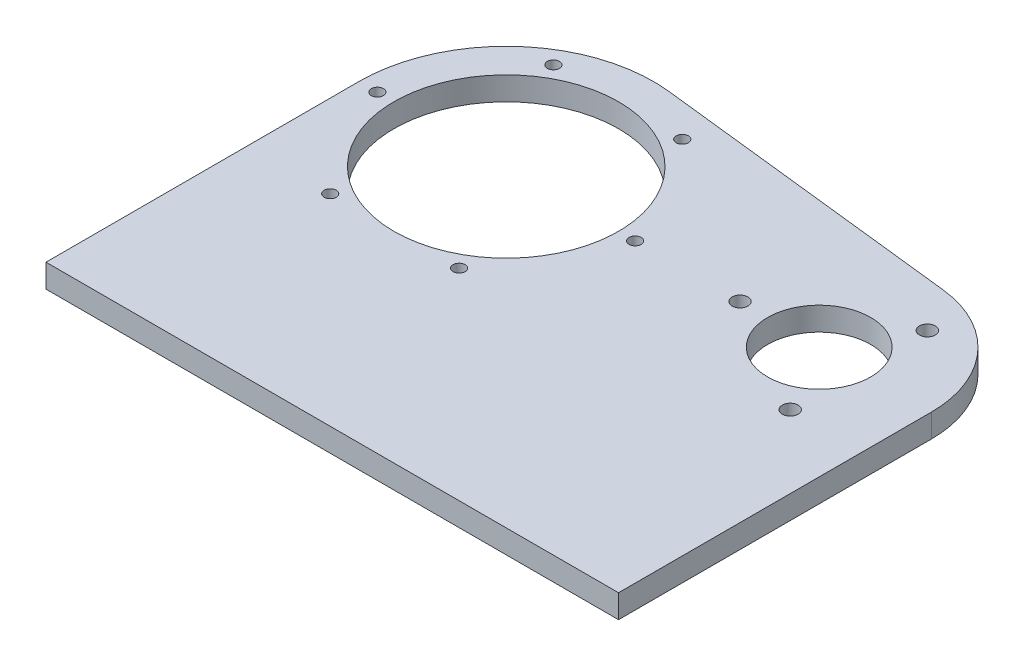
SolidWorks part; units mm, degrees
material "6061 Alloy"
ref_plane "Front Plane" through (0, 0, 0) normal (0, 0, 1) x (1, 0, 0)
ref_plane "Top Plane" through (0, 0, 0) normal (0, 1, 0) x (1, 0, 0)
ref_plane "Right Plane" through (0, 0, 0) normal (1, 0, 0) x (0, 0, -1)
sketch "Sketch1" plane through (0, 0, 0) normal (0, 1, 0) x (1, 0, 0)
  line L0 (4.4706, 39.7494) -> (88.4088, 30.3089)
  line L1 (-40, 40) -> (115.5, 40)
  line L2 (-40, 40) -> (-40, -85)
  line L3 (-40, -85) -> (115.5, -85)
  line L4 (115.5, 40) -> (115.5, -85)
  line L5 (-40, 40) -> (115.5, -85) construction
  line L6 (-40, -85) -> (115.5, 40) construction
  circle A0 centre (0, 0) radius 40
  circle A1 centre (0, 0) radius 30.5
  circle A2 centre (85, 0) radius 14
  circle A3 centre (85, 0) radius 30.5
  point P4 (37.75, -22.5)
  dimension "D3" = 80
  dimension "D4" = 61
  dimension "D5" = 61
  dimension "D6" = 28
  dimension "D1" = 85
  dimension "D7" = 85
extrude "Boss-Extrude1" add sketch "Sketch1" along normal mid plane 6.35 contours L4 A3 L1 A0 L2 L3 | A0 A1 | A3 A2 region at (41.2029, 0, 46.4583) region at (28.9795, 0, -25.9029) region at (107.0969, 0, -19.751)
hole_wizard "M4x0.7 Tapped Hole1" positions "Sketch4" profile "Sketch5" tap size "M4x0.7" standard "ANSI Metric" end condition up to next
sketch "Sketch4" plane through (0, 3.175, 0) normal (0, 1, 0) x (1, 0, 0)
  line L0 (0, 0) -> (35, 0)
  line L1 (0, 0) -> (17.5, -30.3109)
  line L2 (0, 0) -> (-17.5, -30.3109)
  line L3 (0, 0) -> (-35, 0)
  line L4 (0, 0) -> (-17.5, 30.3109)
  line L5 (0, 0) -> (17.5, 30.3109)
  point P5 (35, 0)
  point P16 (17.5, -30.3109)
  point P17 (-17.5, -30.3109)
  point P18 (-35, 0)
  point P19 (-17.5, 30.3109)
  point P20 (17.5, 30.3109)
  dimension "D1" = 35
  dimension "D2" = 6
sketch "Sketch5" plane through (17.5, 3.175, -30.3109) normal (1, 0, 0) x (0, 0, 1)
  line L0 (0, 0) -> (0, 6.35)
  line L1 (0, 6.35) -> (1.65, 6.35)
  line L2 (1.65, 6.35) -> (1.65, 0)
  line L5 (1.65, 0) -> (0, 0)
  line L11 (0, -6.35) -> (0, 107.95) construction
  dimension "Thru Tap Drill Dia." = 3.3
  dimension "Thru Tap Drill Depth" = 6.35
cosmetic thread "Hole Thread1" parameters "D2"=4
cosmetic thread "Hole Thread2" parameters "D2"=4
cosmetic thread "Hole Thread3" parameters "D2"=4
cosmetic thread "Hole Thread4" parameters "D2"=4
cosmetic thread "Hole Thread5" parameters "D2"=4
cosmetic thread "Hole Thread6" parameters "D2"=4
hole_wizard "M4 Clearance Hole1" positions "Sketch6" profile "Sketch7" hole size "M4" standard "ANSI Metric" end condition up to next
sketch "Sketch6" plane through (0, 3.175, 0) normal (0, 1, 0) x (1, 0, 0)
  line L0 (85, 0) -> (95.75, 18.6195)
  line L1 (85, 0) -> (95.75, -18.6195)
  line L2 (85, 0) -> (63.5, 0)
  point P2 (95.75, 18.6195)
  point P10 (95.75, -18.6195)
  point P11 (63.5, 0)
  dimension "D1" = 21.5
  dimension "D2" = 3
sketch "Sketch7" plane through (63.5, 3.175, 0) normal (1, 0, 0) x (0, 0, 1)
  line L0 (0, 0) -> (0, 6.35)
  line L1 (0, 6.35) -> (2.15, 6.35)
  line L2 (2.15, 6.35) -> (2.15, 0)
  line L5 (2.15, 0) -> (0, 0)
  line L11 (0, -6.35) -> (0, 107.95) construction
  dimension "Thru Hole Dia." = 4.3
  dimension "Thru Hole Depth" = 6.35
